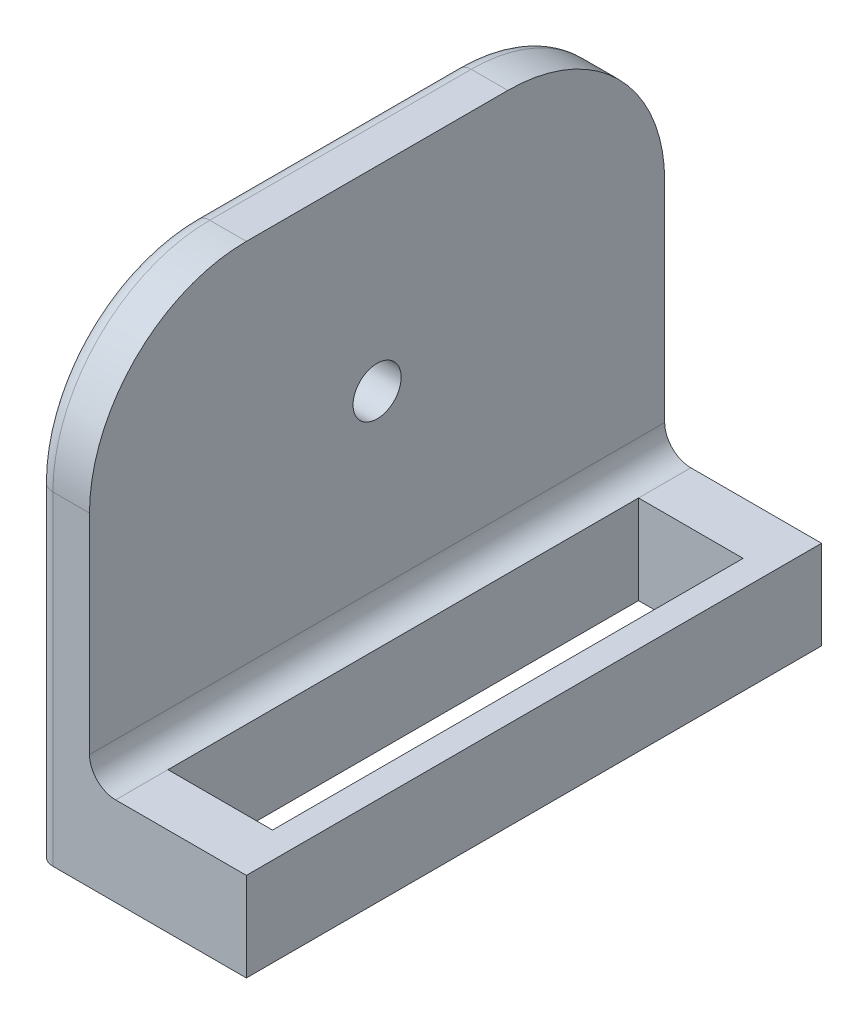
SolidWorks part; units mm, degrees
ref_plane "Front Plane" through (0, 0, 0) normal (0, 0, 1) x (1, 0, 0)
ref_plane "Top Plane" through (0, 0, 0) normal (0, 1, 0) x (1, 0, 0)
ref_plane "Right Plane" through (0, 0, 0) normal (1, 0, 0) x (0, 0, -1)
sketch "Sketch1" plane through (0, 0, 0) normal (0, 1, 0) x (1, 0, 0)
  line L1 (0, 0) -> (40, 0)
  line L2 (0, 0) -> (0, 110)
  line L3 (0, 110) -> (40, 110)
  line L4 (40, 0) -> (40, 110)
  dimension "D1" = 40
  dimension "D2" = 110
extrude "Boss-Extrude1" add sketch "Sketch1" along normal blind 17
sketch "Sketch4" plane through (0, 0, 0) normal (1, 0, 0) x (0, 0, -1)
  line L1 (0, 17) -> (110, 17)
  line L2 (0, 17) -> (0, 92)
  line L3 (0, 92) -> (110, 92)
  line L4 (110, 17) -> (110, 92)
  dimension "D1" = 75
extrude "Boss-Extrude2" add sketch "Sketch4" along normal blind 10
sketch "Sketch5" plane through (0, 17, 0) normal (0, 1, 0) x (1, 0, 0)
  line L0 (25, 0) -> (25, 10) construction
  line L1 (15, 100) -> (35, 100)
  line L2 (15, 100) -> (15, 10)
  line L3 (15, 10) -> (35, 10)
  line L4 (35, 100) -> (35, 10)
  line L5 (10, 0) -> (40, 0) construction
  line L6 (40, 55) -> (35, 55) construction
  line L7 (40, 0) -> (40, 110) construction
  dimension "D1" = 20
  dimension "D2" = 90
extrude "Cut-Extrude1" cut sketch "Sketch5" against normal up to surface (17 mm away) up to face at (20, 0, -55)
sketch "Sketch6" plane through (10, 0, 0) normal (1, 0, 0) x (0, 0, -1)
  line L0 (55, 17) -> (55, 54.7) construction
  line L1 (0, 17) -> (110, 17) construction
  circle A0 centre (55, 54.7) radius 4.6
  dimension "D1" = 37.7
extrude "Cut-Extrude2" cut sketch "Sketch6" against normal up to surface (10 mm away) contours A0 region at (10, 54.7, -55) up to face at (0, 46, -55)
fillet "Fillet1" radius 30 2 edges at (5, 92, 0) (5, 92, -110)
fillet "Fillet2" radius 3 5 edges at (0, 83.2132, -8.7868) (0, 92, -55) (0, 83.2132, -101.2132) (0, 31, 0) (0, 31, -110)
fillet "Fillet3" radius 5 1 edges at (10, 17, -55)
